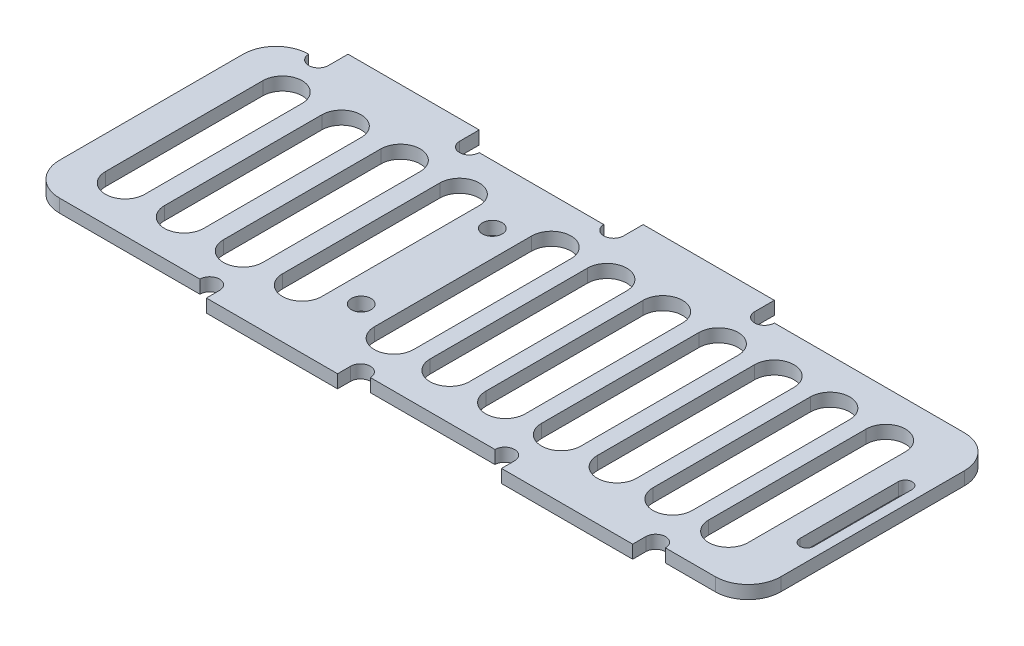
SolidWorks part; units mm, degrees
material "A-玻璃纤维"
ref_plane "前视基准面" through (0, 0, 0) normal (0, 0, 1) x (1, 0, 0)
ref_plane "上视基准面" through (0, 0, 0) normal (0, 1, 0) x (1, 0, 0)
ref_plane "右视基准面" through (0, 0, 0) normal (1, 0, 0) x (0, 0, -1)
sketch "草图1" plane through (0, 0, 0) normal (0, 1, 0) x (1, 0, 0)
  line L1 (-55, 19) -> (55, 19)
  line L2 (-55, 19) -> (-55, -19)
  line L3 (-55, -19) -> (55, -19)
  line L4 (55, 19) -> (55, -19)
  line L5 (0, -19) -> (0, 19) construction
  line L6 (-55, 0) -> (55, 0) construction
  point P0 (0, 0)
  dimension "D1" = 38
  dimension "D2" = 110
extrude "凸台-拉伸1" add sketch "草图1" along normal blind 2
sketch "草图2" plane through (0, 0, -19) normal (0, 0, -1) x (-1, 0, 0)
  line L0 (-55, 2) -> (55, 2) construction
  line L1 (-18, 2) -> (2, 2)
  line L2 (-18, 2) -> (-18, 0)
  line L3 (-18, 0) -> (2, 0)
  line L4 (2, 2) -> (2, 0)
  line L5 (-55, 0) -> (55, 0) construction
  line L6 (-55, 2) -> (-55, 0) construction
  line L8 (47, 0) -> (27, 0)
  line L9 (47, 0) -> (47, 2)
  line L10 (47, 2) -> (27, 2)
  line L11 (27, 0) -> (27, 2)
  dimension "D1" = 37
  dimension "D2" = 20
  dimension "D3" = 20
  dimension "D4" = 45
extrude "凸台-拉伸2" add sketch "草图2" along normal blind 3
sketch "草图4" plane through (0, 0, 19) normal (0, 0, 1) x (1, 0, 0)
  line L0 (-55, 2) -> (55, 2) construction
  line L1 (-25.6, 2) -> (-5.6, 2)
  line L2 (-25.6, 2) -> (-25.6, 0)
  line L3 (-25.6, 0) -> (-5.6, 0)
  line L4 (-5.6, 2) -> (-5.6, 0)
  line L5 (-55, 0) -> (55, 0) construction
  line L7 (55, 2) -> (55, 0) construction
  line L8 (39.4, 0) -> (19.4, 0)
  line L9 (39.4, 0) -> (39.4, 2)
  line L10 (39.4, 2) -> (19.4, 2)
  line L11 (19.4, 0) -> (19.4, 2)
  point P16 (55, 1)
  dimension "D1" = 20
  dimension "D2" = 45
  dimension "D3" = 20
  dimension "D4" = 15.6
extrude "凸台-拉伸3" add sketch "草图4" along normal blind 2
sketch "草图6" plane through (0, 0, 0) normal (0, -1, 0) x (1, 0, 0)
  line L0 (52.45, 7.5) -> (52.45, -7.5) construction
  line L1 (53.5, 7.5) -> (53.5, -7.5)
  line L2 (51.4, 7.5) -> (51.4, -7.5)
  line L3 (55, 19) -> (55, -19) construction
  line L4 (-5.6, 19) -> (19.4, 19) construction
  arc A0 (53.5, 7.5) -> (51.4, 7.5) centre (52.45, 7.5) ccw
  arc A1 (51.4, -7.5) -> (53.5, -7.5) centre (52.45, -7.5) ccw
  point P2 (52.45, 0)
  dimension "D1" = 1.5
  dimension "D2" = 2.1
  dimension "D3" = 15
  dimension "D4" = 19
extrude "切除-拉伸2" cut sketch "草图6" against normal through all
sketch "草图7" plane through (0, 0, 0) normal (0, -1, 0) x (1, 0, 0)
  line L0 (-55, -19) -> (-55, 19) construction
  line L1 (-2, -19) -> (-27, -19) construction
  circle A0 centre (-13, -10) radius 1.5
  circle A1 centre (-13, 10) radius 1.5
  dimension "D1" = 42
  dimension "D3" = 3
  dimension "D2" = 9
  dimension "D5" = 20
extrude "切除-拉伸4" cut sketch "草图7" against normal through all
sketch "草图12" plane through (0, 2, 0) normal (0, 1, 0) x (1, 0, 0)
  line L0 (45, 12) -> (45, -12) construction
  line L1 (48, 12) -> (48, -12)
  line L2 (42, 12) -> (42, -12)
  line L3 (55, -19) -> (55, 19) construction
  line L4 (36.5, 12) -> (36.5, -12) construction
  line L5 (39.5, 12) -> (39.5, -12)
  line L6 (33.5, 12) -> (33.5, -12)
  line L7 (28, 12) -> (28, -12) construction
  line L8 (31, 12) -> (31, -12)
  line L9 (25, 12) -> (25, -12)
  line L10 (19.5, 12) -> (19.5, -12) construction
  line L11 (22.5, 12) -> (22.5, -12)
  line L12 (16.5, 12) -> (16.5, -12)
  line L13 (11, 12) -> (11, -12) construction
  line L14 (14, 12) -> (14, -12)
  line L15 (8, 12) -> (8, -12)
  line L16 (2.5, 12) -> (2.5, -12) construction
  line L17 (5.5, 12) -> (5.5, -12)
  line L18 (-0.5, 12) -> (-0.5, -12)
  line L19 (-20, 12) -> (-20, -12) construction
  line L20 (-6, 12) -> (-6, -12) construction
  line L21 (-3, 12) -> (-3, -12)
  line L22 (-9, 12) -> (-9, -12)
  line L23 (-17, 12) -> (-17, -12)
  line L24 (-23, 12) -> (-23, -12)
  line L25 (-29, 12) -> (-29, -12) construction
  line L26 (-26, 12) -> (-26, -12)
  line L27 (-32, 12) -> (-32, -12)
  line L28 (-38, 12) -> (-38, -12) construction
  line L29 (-35, 12) -> (-35, -12)
  line L30 (-41, 12) -> (-41, -12)
  line L31 (-47, 12) -> (-47, -12) construction
  line L32 (-44, 12) -> (-44, -12)
  line L33 (-50, 12) -> (-50, -12)
  arc A0 (48, 12) -> (42, 12) centre (45, 12) ccw
  arc A1 (42, -12) -> (48, -12) centre (45, -12) ccw
  arc A2 (39.5, 12) -> (33.5, 12) centre (36.5, 12) ccw
  arc A3 (33.5, -12) -> (39.5, -12) centre (36.5, -12) ccw
  arc A4 (31, 12) -> (25, 12) centre (28, 12) ccw
  arc A5 (25, -12) -> (31, -12) centre (28, -12) ccw
  arc A6 (22.5, 12) -> (16.5, 12) centre (19.5, 12) ccw
  arc A7 (16.5, -12) -> (22.5, -12) centre (19.5, -12) ccw
  arc A8 (14, 12) -> (8, 12) centre (11, 12) ccw
  arc A9 (8, -12) -> (14, -12) centre (11, -12) ccw
  arc A11 (5.5, 12) -> (-0.5, 12) centre (2.5, 12) ccw
  arc A12 (-0.5, -12) -> (5.5, -12) centre (2.5, -12) ccw
  arc A13 (-3, 12) -> (-9, 12) centre (-6, 12) ccw
  arc A14 (-9, -12) -> (-3, -12) centre (-6, -12) ccw
  arc A15 (-17, 12) -> (-23, 12) centre (-20, 12) ccw
  arc A16 (-23, -12) -> (-17, -12) centre (-20, -12) ccw
  circle A18 centre (-13, -10) radius 1.5 construction
  arc A19 (-26, 12) -> (-32, 12) centre (-29, 12) ccw
  arc A20 (-32, -12) -> (-26, -12) centre (-29, -12) ccw
  arc A21 (-35, 12) -> (-41, 12) centre (-38, 12) ccw
  arc A22 (-41, -12) -> (-35, -12) centre (-38, -12) ccw
  arc A23 (-44, 12) -> (-50, 12) centre (-47, 12) ccw
  arc A24 (-50, -12) -> (-44, -12) centre (-47, -12) ccw
  point P2 (45, 0)
  point P14 (36.5, 0)
  point P21 (28, 0)
  point P26 (19.5, 0)
  point P33 (11, 0)
  point P41 (2.5, 0)
  point P47 (-20, 0)
  point P50 (-6, 0)
  point P65 (-29, 0)
  point P72 (-38, 0)
  point P73 (-46.2, 0)
  point P80 (-47, 0)
  dimension "D8" = 4
  dimension "D6" = 7
  dimension "D1" = 6
  dimension "D2" = 24
  dimension "D3" = 10
  dimension "D5" = 8.5
  dimension "D7" = 6
  dimension "D9" = 9
  dimension "D4" = 7
sketch "草图13" plane through (0, 2, 0) normal (0, 1, 0) x (1, 0, 0)
  line L0 (-47, 19) -> (-55, 19) construction
  line L1 (-2, 19) -> (-27, 19) construction
  line L2 (55, 19) -> (18, 19) construction
  line L3 (-55, -19) -> (-25.6, -19) construction
  line L4 (-5.6, -19) -> (19.4, -19) construction
  line L5 (39.4, -19) -> (55, -19) construction
  line L6 (-27, 22) -> (-27, 19) construction
  line L7 (-2, 22) -> (-2, 19) construction
  line L8 (18, 22) -> (18, 19) construction
  line L9 (-25.6, -21) -> (-25.6, -19) construction
  line L10 (-5.6, -21) -> (-5.6, -19) construction
  line L11 (19.4, -21) -> (19.4, -19) construction
  line L12 (39.4, -21) -> (39.4, -19) construction
  circle A0 centre (-48.5, 19) radius 1.5
  circle A1 centre (-25.5, 19) radius 1.5
  circle A2 centre (-3.5, 19) radius 1.5
  circle A3 centre (19.5, 19) radius 1.5
  circle A4 centre (-27.1, -19) radius 1.5
  circle A5 centre (-4.1, -19) radius 1.5
  circle A6 centre (17.9, -19) radius 1.5
  circle A7 centre (40.9, -19) radius 1.5
  dimension "D1" = 3
extrude "切除-拉伸6" cut sketch "草图13" against normal through all
fillet "圆角1" radius 5 4 edges at (55, 1, -19) (55, 1, 19) (-55, 1, 19) (-55, 1, -19)
extrude "切除-拉伸8" cut sketch "草图12" against normal through all
